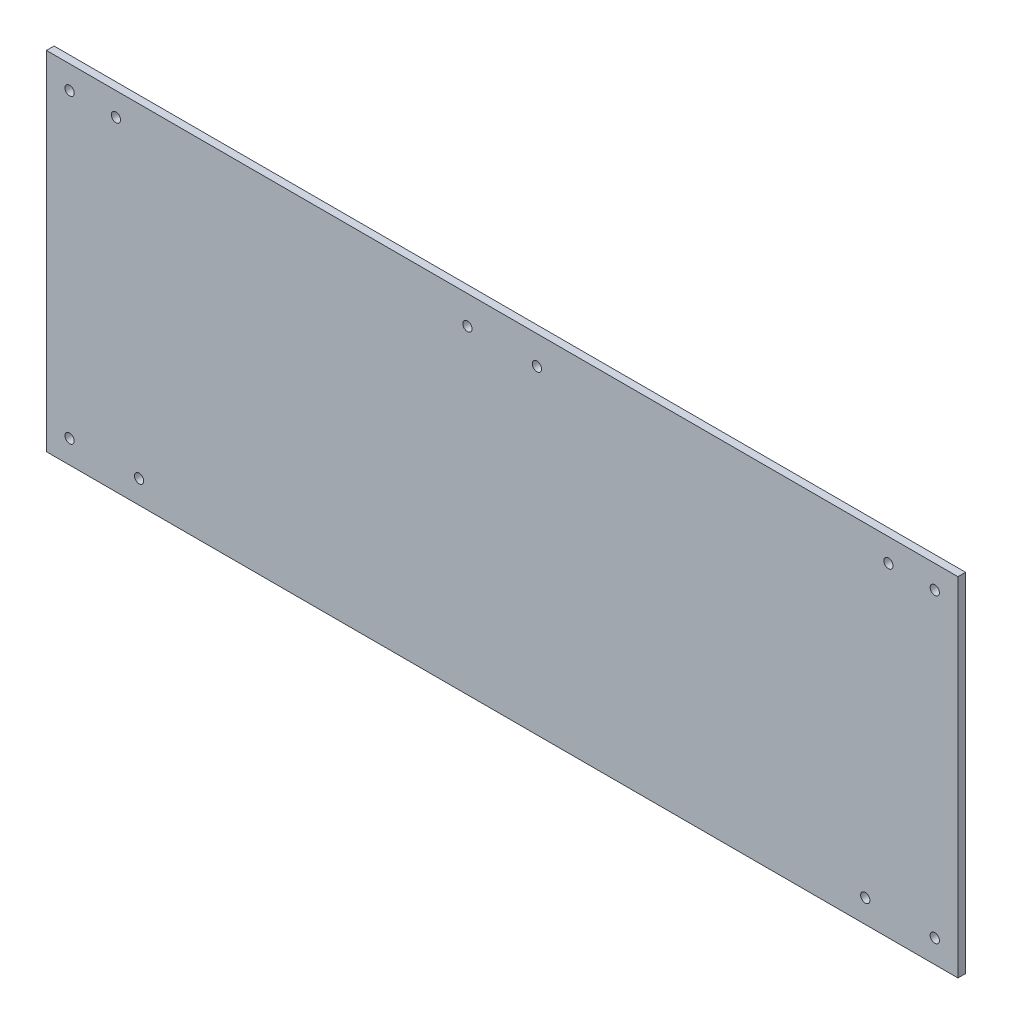
SolidWorks part; units mm, degrees
material "Balsa"
ref_plane "Front Plane" through (0, 0, 0) normal (0, 0, 1) x (1, 0, 0)
ref_plane "Top Plane" through (0, 0, 0) normal (0, 1, 0) x (1, 0, 0)
ref_plane "Right Plane" through (0, 0, 0) normal (1, 0, 0) x (0, 0, -1)
sketch "Sketch1" plane through (0, 0, 0) normal (0, 0, 1) x (1, 0, 0)
  line L0 (223.7, 24.5) -> (223.7, -237.7) construction
  line L1 (-169.7, 24.5) -> (223.7, 24.5)
  line L2 (-169.7, 24.5) -> (-169.7, -125.5)
  line L3 (-169.7, -125.5) -> (223.7, -125.5)
  line L4 (223.7, 24.5) -> (223.7, -125.5)
  line L5 (-169.7, 24.5) -> (223.7, -125.5) construction
  line L6 (-169.7, -125.5) -> (223.7, 24.5) construction
  line L7 (-169.7, -237.7) -> (-169.7, 24.5) construction
  line L8 (-173, 24.5) -> (227, 24.5) construction
  point P4 (27, -50.5)
  dimension "D1" = 150
extrude "Boss-Extrude1" add sketch "Sketch1" along normal blind 3.3
sketch "Sketch2" plane through (0, 0, 0) normal (0, 0, -1) x (-1, 0, 0)
  circle A0 centre (-183.7, -115.5) radius 2
  circle A1 centre (-213.7, -115.5) radius 2
  circle A2 centre (129.7, -115.5) radius 2
  circle A3 centre (159.7, -115.5) radius 2
  dimension "D1" = 4
  dimension "D2" = 4
  dimension "D3" = 4
  dimension "D4" = 4
extrude "Cut-Extrude1" cut sketch "Sketch2" against normal through all
sketch "Sketch3" plane through (0, 0, 3.3) normal (0, 0, 1) x (1, 0, 0)
  line L0 (-169.7, 24.5) -> (-169.7, -125.5) construction
  line L1 (223.7, 24.5) -> (-169.7, 24.5) construction
  line L2 (27, 24.5) -> (27, -125.5) construction
  line L3 (-169.7, -125.5) -> (223.7, -125.5) construction
  circle A0 centre (-159.7, 14.5) radius 2
  circle A1 centre (-139.7, 14.5) radius 2
  circle A2 centre (193.7, 14.5) radius 2
  circle A3 centre (213.7, 14.5) radius 2
  dimension "D1" = 4
  dimension "D2" = 4
  dimension "D3" = 20
  dimension "D4" = 10
  dimension "D5" = 10
  dimension "D6" = 10
extrude "Cut-Extrude2" cut sketch "Sketch3" against normal blind 4
sketch "Sketch4" plane through (0, 0, 3.3) normal (0, 0, 1) x (1, 0, 0)
  line L0 (223.7, 24.5) -> (-169.7, 24.5) construction
  line L1 (0, 24.5) -> (54, 24.5) construction
  line L2 (0, 24.5) -> (0, 0) construction
  line L3 (0, 0) -> (54, 0) construction
  line L4 (54, 24.5) -> (54, 0) construction
  line L5 (0, 24.5) -> (54, 0) construction
  line L6 (0, 0) -> (54, 24.5) construction
  line L7 (0, 24.5) -> (0, 0) construction
  line L8 (54, 0) -> (54, 24.5) construction
  line L9 (27, 24.5) -> (27, 0) construction
  circle A0 centre (12, 12.25) radius 2
  circle A2 centre (42, 12.25) radius 2
  point P4 (27, 12.25)
  dimension "D1" = 4
  dimension "D2" = 15
  dimension "D3" = 12.25
extrude "Cut-Extrude3" cut sketch "Sketch4" against normal blind 4
